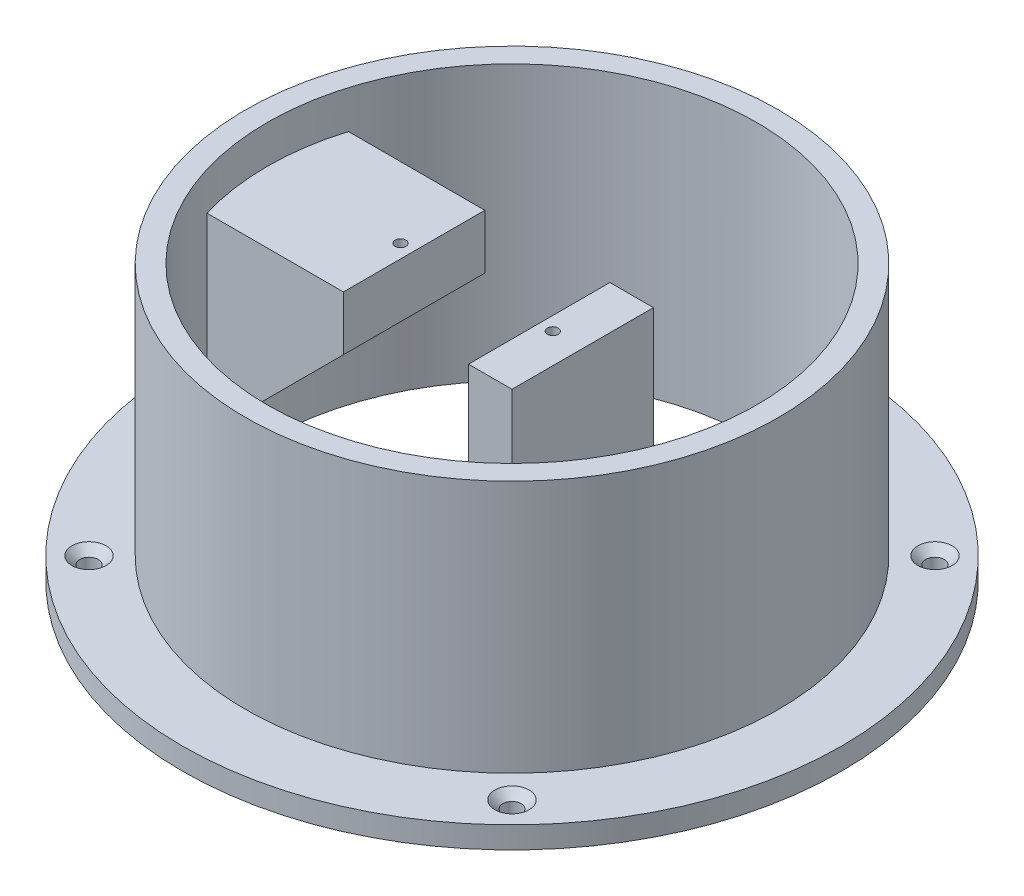
SolidWorks part; units mm, degrees
ref_plane "Front Plane" through (0, 0, 0) normal (0, 0, 1) x (1, 0, 0)
ref_plane "Top Plane" through (0, 0, 0) normal (0, 1, 0) x (1, 0, 0)
ref_plane "Right Plane" through (0, 0, 0) normal (1, 0, 0) x (0, 0, -1)
sketch "Sketch1" plane through (0, 0, 0) normal (0, 1, 0) x (1, 0, 0)
  circle A0 centre (0, 0) radius 60.625
  circle A1 centre (0, 0) radius 45
  dimension "D1" = 121.25
  dimension "D2" = 90
extrude "Boss-Extrude1" add sketch "Sketch1" along normal blind 4
sketch "Sketch2" plane through (0, 4, 0) normal (0, 1, 0) x (1, 0, 0)
  circle A0 centre (0, 0) radius 45 construction
  circle A1 centre (0, 0) radius 45
  circle A2 centre (0, 0) radius 49
  dimension "D1" = 4
extrude "Boss-Extrude2" add sketch "Sketch2" along normal blind 46.5
ref_plane "Plane1" through (0, 30.5, 0) normal (0, 1, 0) x (1, 0, 0)
sketch "Sketch4" plane through (0, 0, 0) normal (0, 0, 1) x (1, 0, 0)
  line L0 (-60.625, 0) -> (60.625, 0) construction
  line L1 (5, 43.5) -> (13, 43.5)
  line L2 (5, 43.5) -> (5, 0)
  line L3 (5, 0) -> (13, 0)
  line L4 (13, 43.5) -> (13, 0)
  line L5 (49, 50.5) -> (-49, 50.5) construction
  line L6 (-45, 50.5) -> (-45, 4)
  line L7 (-18, 43.5) -> (-45, 43.5)
  line L8 (-18, 43.5) -> (-18, 33.5)
  line L9 (-18, 33.5) -> (-45, 33.5)
  line L10 (-45, 43.5) -> (-45, 33.5)
  line L11 (60.625, 4) -> (-60.625, 4) construction
  line L12 (-18, 33.5) -> (-45, 6.5)
  dimension "D1" = 5
  dimension "D2" = 8
  dimension "D3" = 7
  dimension "D4" = 23
  dimension "D5" = 27
  dimension "D6" = 10
  dimension "D7" = 45
  dimension "D8" = 7
extrude "Boss-Extrude4" add sketch "Sketch4" along normal mid plane 26 contours L9 L8 L7 L6 | L12 L9 L6 | L1 L4 L3 L2 region at (-31.5, 38.5, 0) region at (-36, 24.5, 0)
sketch "Sketch5" plane through (0, 0, 0) normal (0, -1, 0) x (1, 0, 0)
  line L0 (3.3931, 14.5721) -> (34.8417, 28.479)
  line L1 (3.3931, -12.7877) -> (35.3292, -27.872)
  line L2 (3.3931, 14.5721) -> (3.3931, -12.7877)
  circle A0 centre (0, 0) radius 45 construction
  arc A1 (35.3292, -27.872) -> (34.8417, 28.479) centre (0, 0) ccw
extrude "Boss-Extrude5" add sketch "Sketch5" against normal up to surface (4 mm away) contours L0 A1 L1 L2 up to face at (0, 4, 60.625)
sketch "Sketch7" plane through (0, 43.5, 0) normal (0, 1, 0) x (1, 0, 0)
  line L0 (-18, -13) -> (-18, 13) construction
  circle A0 centre (-20.5, 5) radius 1.3
  circle A1 centre (-20.5, -5) radius 1.3
  circle A2 centre (27.5, 5) radius 1.3
  circle A3 centre (27.5, -5) radius 1.3
  dimension "D1" = 2.6
  dimension "D2" = 2.6
  dimension "D3" = 10
  dimension "D4" = 5
  dimension "D5" = 2.5
  dimension "D7" = 48
  dimension "D6" = 2
sketch "Sketch12" plane through (0, 4, 0) normal (0, 1, 0) x (1, 0, 0)
  line L3 (11.3931, 7.7188) -> (11.3931, -9.3624)
  line L4 (11.3931, 7.7188) -> (11.3931, -9.3624)
  line L9 (18, 10.8394) -> (18, -12.2841)
  line L10 (13, -13) -> (13, 13) construction
  line L18 (11.3931, -9.3624) -> (32.0457, -18.4953)
  line L19 (32.4985, 17.6875) -> (11.3931, 7.7188)
  line L21 (18, -12.2841) -> (32.0457, -18.4953)
  line L22 (32.4985, 17.6875) -> (18, 10.8394)
  arc A2 (32.0457, -18.4953) -> (32.4985, 17.6875) centre (0, 0) ccw
  arc A3 (32.0457, -18.4953) -> (32.4985, 17.6875) centre (0, 0) ccw
  dimension "D2" = 5
  dimension "D1" = 8
extrude "Cut-Extrude9" cut sketch "Sketch12" against normal through all contours L21 A3 L22 | L22 L9 L21 region at (27.4858, 4, 0.4769)
sketch "Sketch14" plane through (0, 4, 0) normal (0, 1, 0) x (1, 0, 0)
  line L0 (0, 0) -> (-38.8909, 38.8909) construction
  line L1 (5, 13) -> (13, 13) construction
  circle A0 centre (-38.8909, 38.8909) radius 1.5
  circle A1 centre (38.8909, 38.8909) radius 1.5
  circle A2 centre (38.8909, -38.8909) radius 1.5
  circle A3 centre (-38.8909, -38.8909) radius 1.5
  point P15 (0, 0)
  dimension "D1" = 3
  dimension "D2" = 55
  dimension "D3" = 135
  dimension "D4" = 4
hole_wizard "CSK for M3 Countersunk Flat Head Screw1" positions "Sketch15" profile "Sketch17" countersink size "M3" standard "DIN" end condition up to next
sketch "Sketch15" plane through (0, 4, 0) normal (0, 1, 0) x (1, 0, 0)
  point P0 (-38.8909, 38.8909)
  point P3 (-38.8909, -38.8909)
  point P6 (38.8909, -38.8909)
  point P9 (38.8909, 38.8909)
sketch "Sketch17" plane through (-38.8909, 4, -38.8909) normal (1, 0, 0) x (0, 0, 1)
  line L0 (0, 0) -> (0, 4)
  line L1 (0, 4) -> (1.7, 4)
  line L2 (1.7, 4) -> (1.7, 1.45)
  line L3 (1.7, 1.45) -> (3.15, 0)
  line L5 (3.15, 0) -> (0, 0)
  line L6 (-1.7, 1.45) -> (-3.15, 0) construction
  line L11 (0, -6.35) -> (0, 107.95) construction
  dimension "Thru Hole Dia." = 3.4
  dimension "Thru Hole Depth" = 4
  dimension "Near C'Sink Dia." = 6.3
  dimension "Near C'Sink Angle" = 90
sketch "Sketch18" plane through (0, 43.5, 0) normal (0, 1, 0) x (1, 0, 0)
  line L0 (-18, -13) -> (-18, 13) construction
  line L1 (5, -13) -> (5, 13) construction
  circle A0 centre (-20.5, 0) radius 1
  circle A1 centre (7.5, 0) radius 1
  point P4 (-18, 0)
  dimension "D1" = 2.5
  dimension "D2" = 2.5
extrude "Cut-Extrude10" cut sketch "Sketch18" against normal blind 4.5 contours A0
extrude "Cut-Extrude11" cut sketch "Sketch18<3>" against normal blind 4.5
sketch "Sketch18<3>" plane through (0, 43.5, 0) normal (0, 1, 0) x (1, 0, 0) same geometry as "Sketch18"
